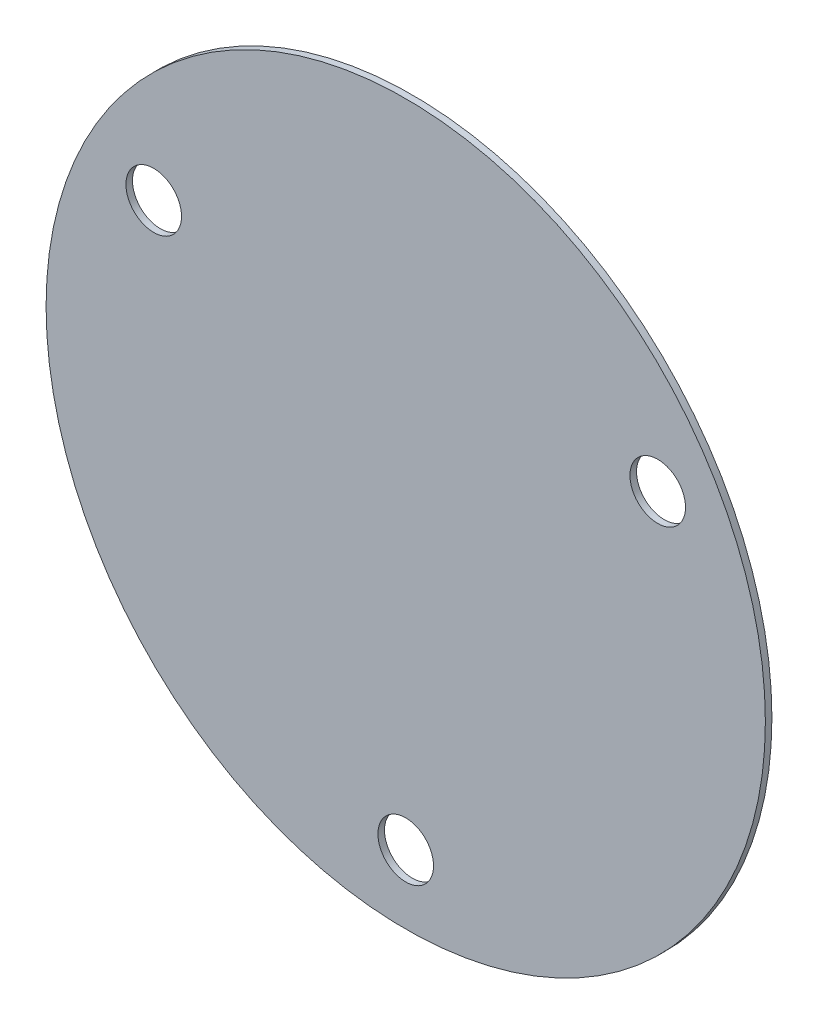
SolidWorks part; units mm, degrees
note: The reader was unsure of these and kept them because the rebuilt part matched: thickness of "Базовая кромка1", "Листовой металл5".
material "Резина"
ref_plane "Спереди" through (0, 0, 0) normal (0, 0, 1) x (1, 0, 0)
ref_plane "Сверху" through (0, 0, 0) normal (0, 1, 0) x (1, 0, 0)
ref_plane "Справа" through (0, 0, 0) normal (1, 0, 0) x (0, 0, -1)
sketch "Эскиз1" plane through (0, 0, 0) normal (0, 0, 1) x (1, 0, 0)
  line L0 (77.0763, 44.5) -> (0, 0) construction
  line L1 (0, 89) -> (0, 0) construction
  circle A0 centre (0, 0) radius 110
  circle A2 centre (0, 89) radius 8.5 construction
  circle A3 centre (0, 0) radius 89 construction
  circle A4 centre (77.0763, 44.5) radius 8.5
  circle A5 centre (77.0763, -44.5) radius 8.5 construction
  circle A6 centre (0, -89) radius 8.5
  circle A7 centre (-77.0763, -44.5) radius 8.5 construction
  circle A8 centre (-77.0763, 44.5) radius 8.5
  point P19 (0, 0)
  point P23 (0, 0)
  dimension "D1" = 220
  dimension "D3" = 17
  dimension "D4" = 178
  dimension "D6" = 60
  dimension "D5" = 6
base flange "Базовая кромка1" sketch "Эскиз1" thickness 2 reverse thickness direction no parameters "D1"=4
sketch "Сгиб-Линии1" [suppressed] plane through (0, 0, 0) normal (0, 1, 0) x (1, 0, 0)
sketch "Граничная рамка1" [suppressed] plane through (0, 0, 0) normal (0, 1, 0) x (1, 0, 0)
sheet metal parameters "Листовой металл5" thickness 2 parameters "D1"=4
flat pattern "Развертка5" [suppressed]
sketch "Сгиб-Линии2" plane through (0, 0, 0) normal (0, 1, 0) x (1, 0, 0)
sketch3d "Граничная рамка2" [suppressed]
  line L0 (109.9501, 110.0498, 0) -> (110.0499, -109.9501, 0) construction
  line L1 (-110.0498, 109.9501, 0) -> (-109.95, -110.0498, 0) construction
  line L2 (109.9501, 110.0498, 0) -> (-110.0498, 109.9501, 0) construction
  line L3 (110.0499, -109.9501, 0) -> (-109.95, -110.0498, 0) construction
